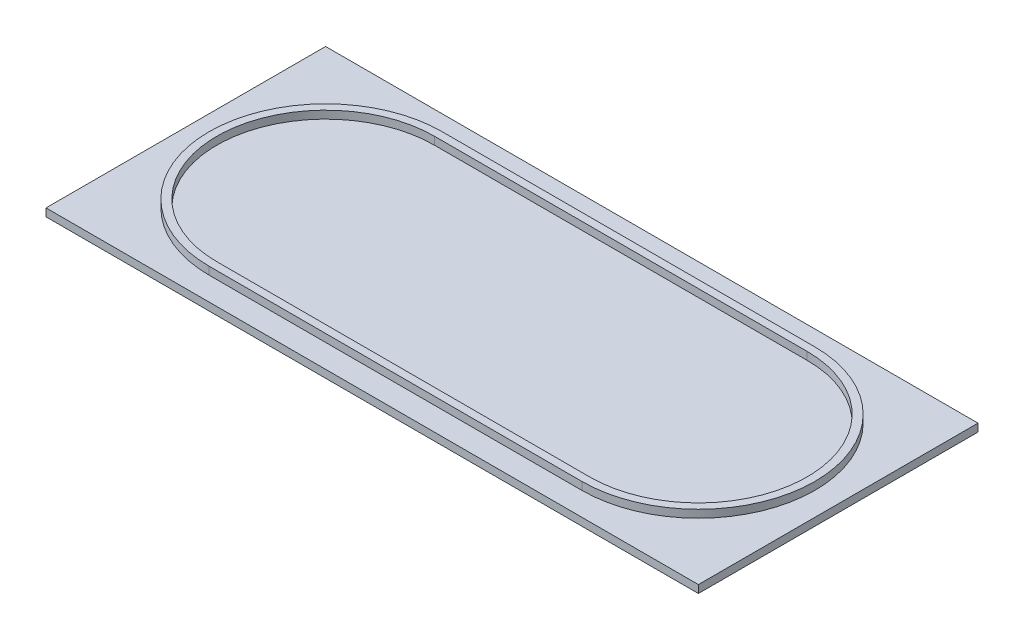
SolidWorks part; units mm, degrees
ref_plane "Front Plane" through (0, 0, 0) normal (0, 0, 1) x (1, 0, 0)
ref_plane "Top Plane" through (0, 0, 0) normal (0, 1, 0) x (1, 0, 0)
ref_plane "Right Plane" through (0, 0, 0) normal (1, 0, 0) x (0, 0, -1)
sketch "Track Sketch" plane through (0, 0, 0) normal (0, 1, 0) x (1, 0, 0)
  line L0 (-304.8, -190.5) -> (304.8, -190.5)
  line L1 (-304.8, -177.8) -> (304.8, -177.8)
  line L3 (-304.8, 177.8) -> (304.8, 177.8)
  line L5 (-304.8, -177.8) -> (304.8, 177.8) construction
  line L6 (-304.8, 177.8) -> (304.8, -177.8) construction
  line L7 (-304.8, 190.5) -> (304.8, 190.5)
  arc A0 (-304.8, 177.8) -> (-304.8, -177.8) centre (-304.8, 0) ccw
  arc A1 (304.8, 177.8) -> (304.8, -177.8) centre (304.8, 0) cw
  arc A2 (304.8, 190.5) -> (304.8, -190.5) centre (304.8, 0) cw
  arc A3 (-304.8, 190.5) -> (-304.8, -190.5) centre (-304.8, 0) ccw
  point P0 (0, 0)
  dimension "D1" = 965.2
  dimension "D2" = 355.6
  dimension "D3" = 12.7
extrude "Train Track" add sketch "Track Sketch" along normal blind 12.7 contours L0 A2 L7 A3 | L1 A1 L3 A0
sketch "Track Base Sketch" plane through (0, 0, 0) normal (0, 1, 0) x (1, 0, 0)
  line L1 (-533.4, -228.6) -> (533.4, -228.6)
  line L2 (-533.4, -228.6) -> (-533.4, 228.6)
  line L3 (-533.4, 228.6) -> (533.4, 228.6)
  line L4 (533.4, -228.6) -> (533.4, 228.6)
  line L5 (-533.4, -228.6) -> (533.4, 228.6) construction
  line L6 (-533.4, 228.6) -> (533.4, -228.6) construction
  point P0 (0, 0)
  dimension "D1" = 1066.8
  dimension "D2" = 457.2
extrude "Track Base" add sketch "Track Base Sketch" against normal blind 12.7 contours L2 L3 L4 L1
equation "\"Track_Length\"= 38"
equation "\"Track_Width\"= 14"
equation "\"D1@Track Sketch\" = \"Track_Length\""
equation "\"D2@Track Sketch\" = \"Track_Width\""
equation "\"Track_Gauge\"= 0.5"
equation "\"D3@Track Sketch\" = \"Track_Gauge\""
equation "\"Support_Width\"= 3"
equation "\"D1@Track Base Sketch\"=\"Track_Length\"+4"
